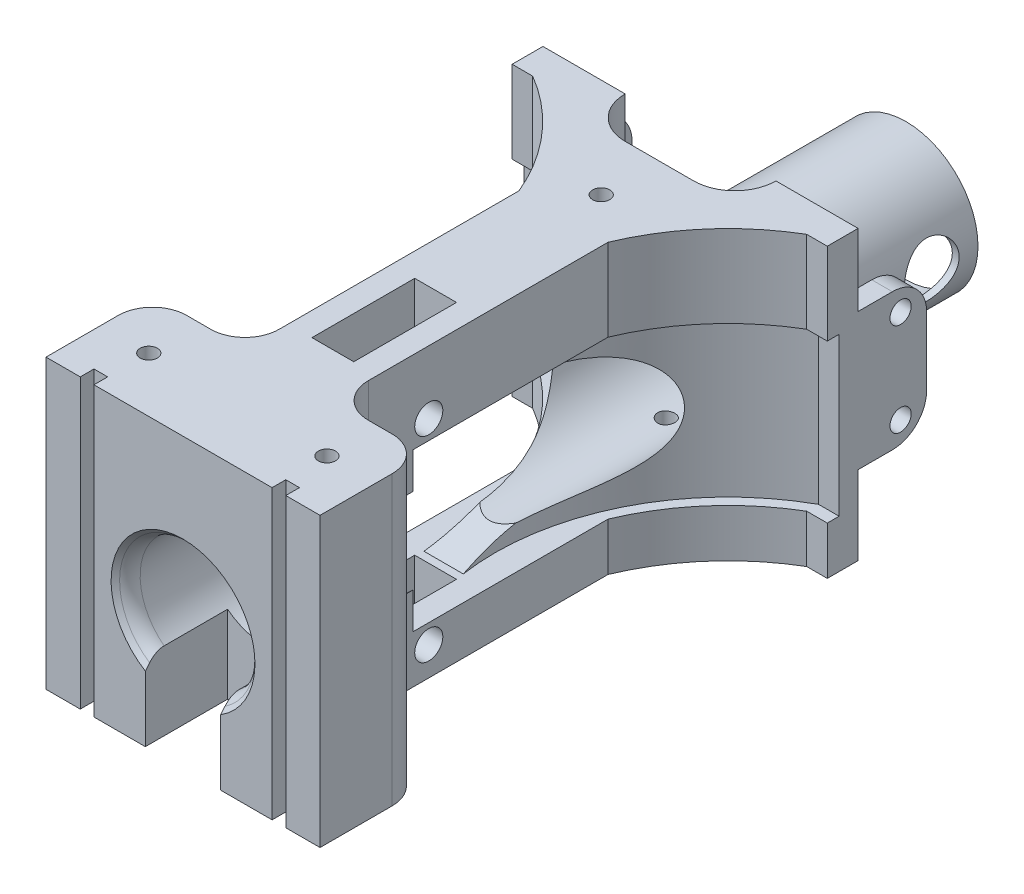
SolidWorks part; units mm, degrees
ref_plane "前视基准面" through (0, 0, 0) normal (0, 0, 1) x (1, 0, 0)
ref_plane "上视基准面" through (0, 0, 0) normal (0, 1, 0) x (1, 0, 0)
ref_plane "右视基准面" through (0, 0, 0) normal (1, 0, 0) x (0, 0, -1)
sketch "草图1" plane through (0, 0, 0) normal (0, 0, 1) x (1, 0, 0)
  line L1 (-20, 23.5) -> (20, 23.5)
  line L2 (-20, 23.5) -> (-20, -23.5)
  line L3 (-20, -23.5) -> (20, -23.5)
  line L4 (20, 23.5) -> (20, -23.5)
  line L5 (-20, 23.5) -> (20, -23.5) construction
  line L6 (-20, -23.5) -> (20, 23.5) construction
  point P0 (0, 0)
  dimension "D1" = 47
  dimension "D2" = 40
extrude "凸台-拉伸1" add sketch "草图1" along normal mid plane 65
sketch "草图2" plane through (0, 23.5, 0) normal (0, 1, 0) x (1, 0, 0)
  line L0 (-36.5, 0) -> (36.5, 0) construction
  line L1 (21.7006, 28.9349) -> (51.2994, 28.9349)
  line L2 (6.5, -27.5) -> (6.5, 12.5)
  line L4 (-6.5, 12.5) -> (-6.5, -27.5)
  line L5 (20, -32.5) -> (-20, -32.5) construction
  line L6 (-51.5217, -27.5) -> (-6.5, -27.5)
  line L8 (-48.5281, 28.9349) -> (-21.7006, 28.9349)
  line L9 (6.5, -27.5) -> (53.8205, -27.5)
  circle A0 centre (36.5, 0) radius 30 construction
  circle A1 centre (-36.5, 0) radius 30 construction
  arc A2 (21.7006, 28.9349) -> (6.5, 12.5) centre (36.5, 0) ccw
  arc A3 (-48.5281, 28.9349) -> (-51.5217, -27.5) centre (-36.5, 0) ccw
  arc A4 (53.8205, -27.5) -> (51.2994, 28.9349) centre (36.5, 0) ccw
  arc A5 (-6.5, 12.5) -> (-21.7006, 28.9349) centre (-36.5, 0) ccw
  point P3 (0, 0)
  dimension "D2" = 60
  dimension "D3" = 65
  dimension "D1" = 73
  dimension "D4" = 5
extrude "切除-拉伸1" cut sketch "草图2" against normal through all
sketch "草图3" plane through (0, 0, 32.5) normal (0, 0, 1) x (1, 0, 0)
  circle A0 centre (0, 0) radius 9
  dimension "D1" = 18
extrude "切除-拉伸2" cut sketch "草图3" against normal through all
sketch "草图4" plane through (0, 0, 0) normal (0, 1, 0) x (1, 0, 0)
  line L1 (56.4937, -27.5) -> (16.5063, -27.5)
  line L2 (-20, -27.5) -> (-6.5, -27.5) construction
  line L3 (52.5, 30) -> (20.5, 30)
  line L5 (-20.5, 30) -> (-52.5, 30)
  line L6 (-16.5063, -27.5) -> (-56.4937, -27.5)
  arc A1 (56.4937, -27.5) -> (52.5, 30) centre (36.5, 0) ccw
  arc A2 (-52.5, 30) -> (-56.4937, -27.5) centre (-36.5, 0) ccw
  arc A3 (-16.5063, -27.5) -> (-20.5, 30) centre (-36.5, 0) ccw
  arc A4 (20.5, 30) -> (16.5063, -27.5) centre (36.5, 0) ccw
  point P8 (36.5, 0)
  point P12 (-36.5, 0)
  dimension "D2" = 34
  dimension "D3" = 34
  dimension "D1" = 73
  dimension "D4" = 36.5
  dimension "D5" = 30
extrude "切除-拉伸3" cut sketch "草图4" against normal mid plane 23
sketch "草图7" plane through (-6.5, 0, 0) normal (-1, 0, 0) x (0, 0, 1)
  circle A1 centre (13.6704, 14.3) radius 2.05
  dimension "D1" = 13.6704
  dimension "D2" = 4.1
  dimension "D3" = 13.6704
  dimension "D4" = 14.3
extrude "切除-拉伸5" cut sketch "草图7" against normal through all
mirror "镜向1" about plane through (0, 0, 0) normal (0, 1, 0) of "切除-拉伸5"
sketch "草图9" plane through (6.5, 0, 0) normal (1, 0, 0) x (0, 0, -1)
  line L0 (-16, -11.5) -> (12.5, -11.5) construction
  line L1 (-16, 11.5) -> (-5, 11.5)
  line L2 (-16, 11.5) -> (-16, -11.5)
  line L3 (-16, -11.5) -> (-5, -11.5)
  line L4 (-5, 11.5) -> (-5, -11.5)
  line L5 (29.7279, -11.5) -> (-16, -11.5) construction
  dimension "D1" = 11
extrude "切除-拉伸7" cut sketch "草图9" against normal through all
sketch "草图10" plane through (0, 0, -32.5) normal (0, 0, -1) x (-1, 0, 0)
  circle A0 centre (0, 0) radius 9.5
  dimension "D1" = 19
extrude "切除-拉伸8" cut sketch "草图10" against normal up to next
sketch "草图12" plane through (0, 23.5, 0) normal (0, 1, 0) x (1, 0, 0)
  line L0 (20, -32.5) -> (-20, -32.5) construction
  line L1 (-3.05, -6.17) -> (3.05, -6.17)
  line L2 (-3.05, -6.17) -> (-3.05, -21.17)
  line L3 (-3.05, -21.17) -> (3.05, -21.17)
  line L4 (3.05, -6.17) -> (3.05, -21.17)
  line L5 (-3.05, -6.17) -> (3.05, -21.17) construction
  line L6 (-3.05, -21.17) -> (3.05, -6.17) construction
  point P0 (0, -13.67)
  dimension "D1" = 18.83
  dimension "D2" = 15
  dimension "D3" = 6.1
extrude "切除-拉伸9" cut sketch "草图12" against normal through all
fillet "圆角4" [suppressed] radius 1
fillet "圆角5" [suppressed] radius 5
sketch "草图13" plane through (0, 0, 32.5) normal (0, 0, 1) x (1, 0, 0)
  line L4 (20, -23.5) -> (20, 23.5)
  line L5 (20, 23.5) -> (-20, 23.5)
  line L6 (-20, 23.5) -> (-20, -23.5)
  line L7 (-20, -23.5) -> (20, -23.5)
  line L8 (20, -23.5) -> (20, 23.5)
  line L9 (20, 23.5) -> (-20, 23.5)
  line L10 (-20, 23.5) -> (-20, -23.5)
  line L11 (-20, -23.5) -> (20, -23.5)
  circle A0 centre (0, 0) radius 9 construction
  circle A1 centre (0, 0) radius 9
  dimension "D1" = 0
extrude "凸台-拉伸2" add sketch "草图13" along normal blind 10.54
sketch "草图14" plane through (0, 0, 43.04) normal (0, 0, 1) x (1, 0, 0)
  line L0 (0, 0) -> (0, 30.6084) construction
  line L1 (14, -23.5) -> (14, 23.5) construction
  line L4 (15, -23.5) -> (15, 23.5)
  line L6 (13, -23.5) -> (13, 23.5)
  line L7 (13, 23.5) -> (15, 23.5)
  line L8 (20, 23.5) -> (-20, 23.5) construction
  line L9 (13, -23.5) -> (15, -23.5)
  line L10 (-20, -23.5) -> (20, -23.5) construction
  line L13 (15, 0) -> (15, 30.6084) construction
  line L14 (14, 0) -> (14, 30.6084) construction
  line L15 (13, 0) -> (13, 30.6084) construction
  dimension "D2" = 2
  dimension "D3" = 1
  dimension "D1" = 14
extrude "切除-拉伸10" cut sketch "草图14" against normal blind 2
mirror "镜向2" about plane through (0, 0, 0) normal (1, 0, 0) of "切除-拉伸10"
sketch "草图15" plane through (0, 0, 43.04) normal (0, 0, 1) x (1, 0, 0)
  line L0 (-20, -23.5) -> (-15, -23.5) construction
  line L1 (-20, -23.5) -> (20, -23.5)
  line L2 (-20, -23.5) -> (-20, -18.7)
  line L3 (-20, -18.7) -> (20, -18.7)
  line L4 (20, -23.5) -> (20, -18.7)
  line L5 (-20, 23.5) -> (-20, -23.5) construction
  line L6 (20, -23.5) -> (20, 23.5) construction
  dimension "D1" = 4.8
extrude "切除-拉伸11" cut sketch "草图15" against normal through all
sketch "草图16" plane through (0, -18.7, 0) normal (0, -1, 0) x (1, 0, 0)
  line L0 (13, 43.04) -> (-13, 43.04) construction
  line L1 (-5.5, 43.04) -> (5.5, 43.04)
  line L2 (-5.5, 43.04) -> (-5.5, 31.04)
  line L3 (-5.5, 31.04) -> (5.5, 31.04)
  line L4 (5.5, 43.04) -> (5.5, 31.04)
  line L5 (-5.5, 43.04) -> (5.5, 31.04) construction
  line L6 (-5.5, 31.04) -> (5.5, 43.04) construction
  point P0 (0, 37.04)
  dimension "D1" = 11
  dimension "D2" = 12
extrude "切除-拉伸12" cut sketch "草图16" against normal up to surface (11.5761 mm away) up to face at (0, 0, 20.1675)
sketch "草图17" plane through (0, -18.7, 0) normal (0, -1, 0) x (1, 0, 0)
  line L0 (10, 37.04) -> (-10, 37.04) construction
  line L2 (9, 43.04) -> (-9, 43.04) construction
  circle A0 centre (-10, 37.04) radius 1.25
  circle A1 centre (10, 37.04) radius 1.25
  point P2 (0, 37.04)
  dimension "D3" = 2.5
  dimension "D1" = 20
  dimension "D2" = 6
extrude "切除-拉伸13" cut sketch "草图17" against normal blind 10
cosmetic thread "装饰螺纹线5" parameters "D2"=3
cosmetic thread "装饰螺纹线6" parameters "D2"=3
sketch "草图18" plane through (0, 0, 43.04) normal (0, 0, 1) x (1, 0, 0)
  line L0 (0, 0) -> (0, -18.7) construction
  line L1 (-5.5, -18.7) -> (5.5, -18.7) construction
  line L3 (6.5, -12) -> (13.5, -12)
  line L4 (6.5, -12) -> (6.5, -15.2)
  line L5 (6.5, -15.2) -> (13.5, -15.2)
  line L6 (13.5, -12) -> (13.5, -15.2)
  dimension "D1" = 7
  dimension "D2" = 3.2
  dimension "D3" = 6.5
  dimension "D4" = 12
extrude "切除-拉伸14" [suppressed] cut sketch "草图18" against normal blind 38
mirror "镜向3" [suppressed] about plane through (0, 0, 0) normal (1, 0, 0)
fillet "圆角7" radius 5 2 edges at (6.5, -12.4625, 27.5) (-6.5, -12.4625, 27.5)
chamfer "倒角1" distance 1.5 angle 45 1 edges at (0, 9, 43.04)
fillet "圆角8" radius 3 1 edges at (0, 9, 41.54)
chamfer "倒角2" [suppressed] distance 1.5 angle 45
sketch "草图19" plane through (0, 11.5, 0) normal (0, -1, 0) x (1, 0, 0)
  line L0 (-3.05, 16) -> (-6.5, 16)
  line L1 (-6.5, 16) -> (-6.5, 11)
  line L2 (-6.5, -12.5) -> (-6.5, 22.5) construction
  line L3 (-6.5, 11) -> (-3.05, 11)
  line L4 (-3.05, 21.17) -> (-3.05, 6.17) construction
  line L5 (-3.05, 11) -> (-3.05, 16)
  line L6 (3.05, 16) -> (6.5, 16)
  line L7 (6.5, 22.5) -> (6.5, -12.5) construction
  line L8 (6.5, 16) -> (6.5, 11)
  line L9 (6.5, 11) -> (3.05, 11)
  line L10 (3.05, 6.17) -> (3.05, 21.17) construction
  line L11 (3.05, 11) -> (3.05, 16)
  dimension "D1" = 5
extrude "凸台-拉伸3" [suppressed] add sketch "草图19" along normal blind 1.5
mirror "镜向8" [suppressed] about plane through (0, 0, 0) normal (0, 1, 0)
fillet "圆角9" [suppressed] radius 10
fillet "圆角10" [suppressed] radius 1.5
sketch "草图20" plane through (-20, 0, 0) normal (-1, 0, 0) x (0, 0, 1)
  line L0 (-32.5, 23.5) -> (-32.5, -18.7) construction
  line L1 (-37.5, 12.9983) -> (-32.5, 12.9983)
  line L2 (-42.5, 7.9983) -> (-42.5, -2.0017)
  line L3 (-37.5, -7.0017) -> (-32.5, -7.0017)
  line L4 (-32.5, 12.9983) -> (-32.5, -7.0017)
  line L5 (-38.7, 9.8) -> (-38.7, -3.8) construction
  line L14 (-32.5, 23.5) -> (-32.5, -18.7)
  line L15 (-32.5, -18.7) -> (-28, -18.7)
  line L16 (-28, -18.7) -> (-28, -11.5)
  line L17 (-28, -18.7) -> (-28, -11.5)
  line L18 (-29.7279, -11.5) -> (-29.7279, 11.5)
  line L19 (-28, -11.5) -> (-29.7279, -11.5)
  line L20 (-28, -11.5) -> (-29.7279, -11.5)
  line L21 (-28, 23.5) -> (-32.5, 23.5)
  line L22 (-32.5, 23.5) -> (-32.5, -18.7)
  line L23 (-32.5, -18.7) -> (-28, -18.7)
  line L26 (-29.7279, -11.5) -> (-29.7279, 11.5)
  line L29 (-28, 23.5) -> (-32.5, 23.5)
  line L30 (-29.7279, 11.5) -> (-28, 11.5)
  line L31 (-29.7279, 11.5) -> (-28, 11.5)
  line L32 (-28, 11.5) -> (-28, 23.5)
  line L33 (-28, 11.5) -> (-28, 23.5)
  circle A0 centre (-38.7, -3.8) radius 1.55
  circle A1 centre (-38.7, 9.8) radius 1.55
  arc A2 (-37.5, 12.9983) -> (-42.5, 7.9983) centre (-37.5, 7.9983) ccw
  arc A3 (-42.5, -2.0017) -> (-37.5, -7.0017) centre (-37.5, -2.0017) ccw
  point P10 (-32.5, 2.9983)
  point P15 (-42.5, 12.9983)
  point P18 (-42.5, -7.0017)
  line M2 (-32.5, 23.5) -> (-32.5, -18.7)
  line M3 (-32.5, -18.7) -> (-28, -18.7)
  line M4 (-28, -18.7) -> (-28, -11.5)
  line M5 (-28, -11.5) -> (-29.7279, -11.5)
  line M6 (-29.7279, -11.5) -> (-29.7279, 11.5)
  line M7 (-29.7279, 11.5) -> (-28, 11.5)
  line M8 (-28, 11.5) -> (-28, 23.5)
  line M9 (-28, 23.5) -> (-32.5, 23.5)
  dimension "D1" = 3.1
  dimension "D5" = 9.8
  dimension "D8" = 5
  dimension "D2" = 2.9983
  dimension "D3" = 38.7
  dimension "D4" = 13.6
  dimension "D6" = 20
  dimension "D7" = 10
  dimension "D9" = 0
extrude "凸台-拉伸5" add sketch "草图20" along normal blind 3 contours M9 M2 M3 M4 M5 M6 M7 M8 | L2 A3 L3 L1 A2 A1 A0 M2 region at (-20, 2.9981, -37.1568) region at (-20, 3.0352, -30.6168)
mirror "镜向9" about plane through (0, 0, 0) normal (1, 0, 0) of "凸台-拉伸5"
sketch "草图21" plane through (0, 0, -32.5) normal (0, 0, -1) x (-1, 0, 0)
  circle A0 centre (0, 0) radius 9.5
  circle A1 centre (0, 0) radius 10.5
  dimension "D1" = 21
  dimension "D2" = 19
extrude "凸台-拉伸6" add sketch "草图21" along normal up to surface (10 mm away) up to face at (21.5, 2.9983, -42.5)
sketch "草图22" plane through (20, 0, 0) normal (1, 0, 0) x (0, 0, -1)
  line L0 (-43.04, 23.5) -> (-27.5, 23.5) construction
  line L1 (-38.04, 18.5) -> (-32.04, 18.5)
  line L2 (-38.04, 18.5) -> (-38.04, 15.3)
  line L3 (-38.04, 15.3) -> (-32.04, 15.3)
  line L4 (-32.04, 18.5) -> (-32.04, 15.3)
  line L5 (-43.04, -18.7) -> (-43.04, 23.5) construction
  dimension "D1" = 6
  dimension "D2" = 3.2
  dimension "D3" = 5
  dimension "D4" = 5
extrude "切除-拉伸15" [suppressed] cut sketch "草图22" against normal through all
sketch "草图23" plane through (0, 23.5, 0) normal (0, 1, 0) x (1, 0, 0)
  line L0 (-13, -35.04) -> (13, -35.04) construction
  line L1 (20, -43.04) -> (15, -43.04) construction
  circle A0 centre (13, -35.04) radius 1.25
  circle A1 centre (-13, -35.04) radius 1.25
  point P2 (0, -35.04)
  dimension "D3" = 2.5
  dimension "D1" = 26
  dimension "D2" = 8
extrude "切除-拉伸16" cut sketch "草图23" against normal blind 10
cosmetic thread "装饰螺纹线1" parameters "D2"=3
cosmetic thread "装饰螺纹线2" parameters "D2"=3
sketch "草图26" plane through (0, 0, -32.5) normal (0, 0, -1) x (-1, 0, 0)
  line L0 (-23, -18.7) -> (23, -18.7) construction
  line L1 (-3, -12.5) -> (3, -12.5)
  line L2 (-3, -12.5) -> (-3, -15.7)
  line L3 (-3, -15.7) -> (3, -15.7)
  line L4 (3, -12.5) -> (3, -15.7)
  line L5 (-3, -12.5) -> (3, -15.7) construction
  line L6 (-3, -15.7) -> (3, -12.5) construction
  point P0 (0, -14.1)
  dimension "D1" = 3.2
  dimension "D2" = 6
  dimension "D3" = 3
extrude "切除-拉伸19" [suppressed] cut sketch "草图26" against normal blind 10
sketch "草图27" plane through (0, -18.7, 0) normal (0, -1, 0) x (1, 0, 0)
  line L0 (23, -32.5) -> (-23, -32.5) construction
  circle A0 centre (0, -27.5) radius 1.25
  dimension "D1" = 2.5
  dimension "D2" = 5
extrude "切除-拉伸20" cut sketch "草图27" against normal blind 10
cosmetic thread "装饰螺纹线4" parameters "D2"=3
fillet "圆角11" radius 5 2 edges at (-20, 2.4, 27.5) (20, 2.4, 27.5)
sketch "草图28" plane through (0, 23.5, 0) normal (0, 1, 0) x (1, 0, 0)
  line L1 (-5, 32.5) -> (5, 32.5) construction
  line L2 (23, 32.5) -> (-23, 32.5) construction
  line L3 (-5, 38.5) -> (5, 38.5)
  line L4 (-5, 26.5) -> (5, 26.5)
  arc A1 (-5, 38.5) -> (-5, 26.5) centre (-5, 32.5) ccw
  arc A2 (5, 26.5) -> (5, 38.5) centre (5, 32.5) ccw
  point P4 (0, 32.5)
  dimension "D1" = 10
  dimension "D2" = 6
extrude "切除-拉伸21" cut sketch "草图28" against normal blind 10
sketch "草图30" [suppressed] plane through (0, 0, 0) normal (1, 0, 0) x (0, 0, -1)
  line L0 (-32.5, 18.5) -> (-38.04, 18.5) construction
  line L1 (15, 18.5) -> (21, 18.5)
  line L2 (15, 18.5) -> (15, 15.3)
  line L3 (15, 15.3) -> (21, 15.3)
  line L4 (21, 18.5) -> (21, 15.3)
  dimension "D1" = 3.2
  dimension "D2" = 6
  dimension "D3" = 15
extrude "切除-拉伸22" [suppressed] cut sketch "草图30" against normal mid plane 55
sketch "草图31" plane through (0, 23.5, 0) normal (0, 1, 0) x (1, 0, 0)
  circle A0 centre (0, 18) radius 1.25
  dimension "D1" = 2.5
  dimension "D2" = 18
extrude "切除-拉伸23" cut sketch "草图31" against normal blind 10
cosmetic thread "装饰螺纹线3" parameters "D2"=3
sketch "草图32" plane through (0, -18.7, 0) normal (0, -1, 0) x (1, 0, 0)
  line L24 (-20, 43.04) -> (-20, 32.5)
  line L25 (-15, 27.5) -> (-11.5, 27.5)
  line L26 (-6.5, 22.5) -> (-6.5, -12.5)
  line L27 (-20, -28) -> (-23, -28)
  line L28 (-23, -28) -> (-23, -32.5)
  line L29 (-23, -32.5) -> (23, -32.5)
  line L30 (23, -32.5) -> (23, -28)
  line L32 (6.5, -12.5) -> (6.5, 22.5)
  line L33 (11.5, 27.5) -> (15, 27.5)
  line L34 (20, 32.5) -> (20, 43.04)
  line L35 (20, 43.04) -> (15, 43.04)
  line L36 (15, 43.04) -> (15, 41.04)
  line L37 (15, 41.04) -> (13, 41.04)
  line L38 (13, 41.04) -> (13, 43.04)
  line L39 (13, 43.04) -> (5.5, 43.04)
  line L40 (5.5, 43.04) -> (5.5, 31.04)
  line L41 (5.5, 31.04) -> (-5.5, 31.04)
  line L42 (-5.5, 31.04) -> (-5.5, 43.04)
  line L43 (-5.5, 43.04) -> (-13, 43.04)
  line L44 (-13, 43.04) -> (-13, 41.04)
  line L45 (-13, 41.04) -> (-15, 41.04)
  line L46 (-15, 41.04) -> (-15, 43.04)
  line L47 (-15, 43.04) -> (-20, 43.04)
  line L48 (-20, 43.04) -> (-20, 32.5)
  line L49 (-15, 27.5) -> (-11.5, 27.5)
  line L50 (-6.5, 22.5) -> (-6.5, -12.5)
  line L52 (-23, -28) -> (-23, -32.5)
  line L53 (-23, -32.5) -> (23, -32.5)
  line L54 (23, -32.5) -> (23, -28)
  line L56 (6.5, -12.5) -> (6.5, 22.5)
  line L57 (11.5, 27.5) -> (15, 27.5)
  line L58 (20, 32.5) -> (20, 43.04)
  line L59 (20, 43.04) -> (15, 43.04)
  line L60 (15, 43.04) -> (15, 41.04)
  line L61 (15, 41.04) -> (13, 41.04)
  line L62 (13, 41.04) -> (13, 43.04)
  line L63 (13, 43.04) -> (5.5, 43.04)
  line L64 (5.5, 43.04) -> (5.5, 31.04)
  line L65 (5.5, 31.04) -> (-5.5, 31.04)
  line L66 (-5.5, 31.04) -> (-5.5, 43.04)
  line L67 (-5.5, 43.04) -> (-13, 43.04)
  line L68 (-13, 43.04) -> (-13, 41.04)
  line L69 (-13, 41.04) -> (-15, 41.04)
  line L70 (-15, 41.04) -> (-15, 43.04)
  line L71 (-15, 43.04) -> (-20, 43.04)
  line L72 (-20, -28) -> (-23, -28)
  line L74 (23, -28) -> (20, -28)
  line L75 (23, -28) -> (20, -28)
  arc A6 (-20, 32.5) -> (-15, 27.5) centre (-15, 32.5) ccw
  arc A7 (-6.5, 22.5) -> (-11.5, 27.5) centre (-11.5, 22.5) ccw
  arc A8 (-20, -28) -> (-6.5, -12.5) centre (-36.5, 0) ccw
  arc A10 (11.5, 27.5) -> (6.5, 22.5) centre (11.5, 22.5) ccw
  arc A11 (15, 27.5) -> (20, 32.5) centre (15, 32.5) ccw
  arc A12 (-20, 32.5) -> (-15, 27.5) centre (-15, 32.5) ccw
  arc A13 (-6.5, 22.5) -> (-11.5, 27.5) centre (-11.5, 22.5) ccw
  arc A16 (11.5, 27.5) -> (6.5, 22.5) centre (11.5, 22.5) ccw
  arc A17 (15, 27.5) -> (20, 32.5) centre (15, 32.5) ccw
  arc A18 (-20, -28) -> (-6.5, -12.5) centre (-36.5, 0) ccw
  arc A20 (6.5, -12.5) -> (20, -28) centre (36.5, 0) ccw
  arc A21 (6.5, -12.5) -> (20, -28) centre (36.5, 0) ccw
  dimension "D1" = 0
extrude "切除-拉伸24" cut sketch "草图32" against normal blind 0.2
sketch "草图33" plane through (0, 0, -32.5) normal (0, 0, -1) x (-1, 0, 0)
  circle A0 centre (0, 0) radius 10.5
  circle A1 centre (0, 0) radius 9.5
  dimension "D1" = 19
  dimension "D2" = 21
extrude "凸台-拉伸7" add sketch "草图33" along normal blind 30
sketch "草图34" plane through (0, 0, 0) normal (1, 0, 0) x (0, 0, -1)
  line L0 (32.5, 23.5) -> (32.5, 12.9983) construction
  circle A0 centre (55.75, 0) radius 4
  dimension "D1" = 8
  dimension "D2" = 23.25
extrude "切除-拉伸25" cut sketch "草图34" against normal through all both and the other way through all
sketch "草图35" plane through (-6.5, 0, 0) normal (-1, 0, 0) x (0, 0, 1)
  line L0 (-5, -8.5) -> (5, -11.5)
  line L1 (5, -11.5) -> (-5, -11.5) construction
  line L4 (-5, -11.5) -> (-5, -8.5) construction
  line L5 (-5, -8.5) -> (5, -8.5)
  line L6 (5, -8.5) -> (5, -11.5)
  dimension "D1" = 3
  dimension "D2" = 10
extrude "切除-拉伸26" cut sketch "草图35" against normal through all
mirror "镜向10" about plane through (0, 0, 0) normal (0, 1, 0) of "切除-拉伸26"
fillet "圆角12" [suppressed] radius 1.5
